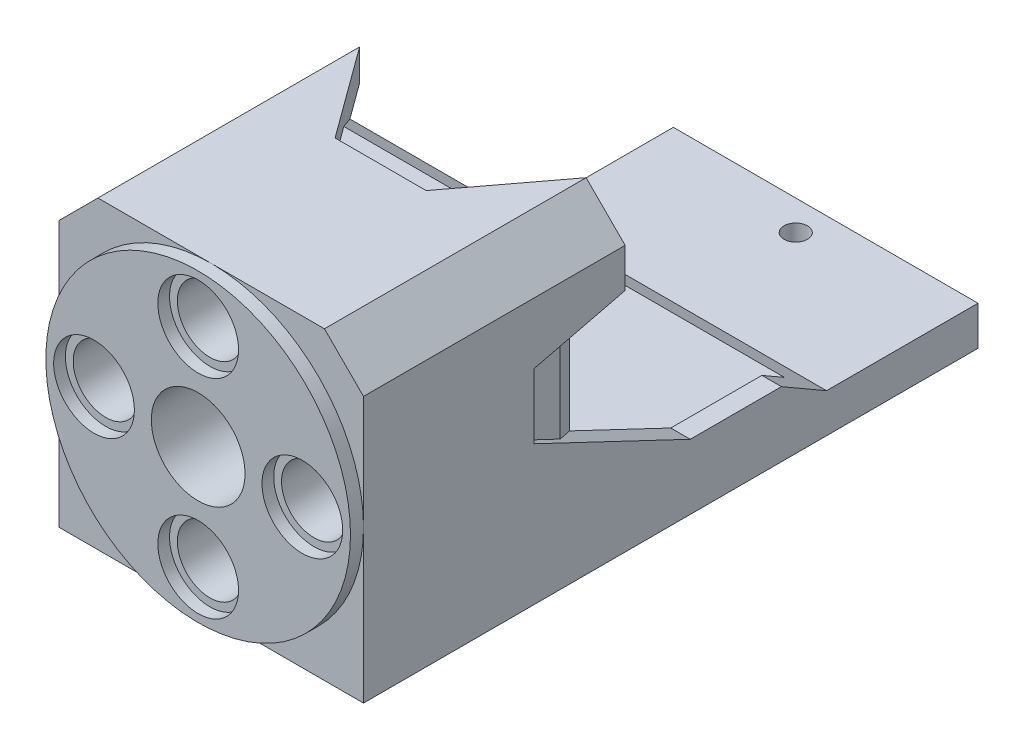
SolidWorks part; units mm, degrees
ref_plane "前视基准面" through (0, 0, 0) normal (0, 0, 1) x (1, 0, 0)
ref_plane "上视基准面" through (0, 0, 0) normal (0, 1, 0) x (1, 0, 0)
ref_plane "右视基准面" through (0, 0, 0) normal (1, 0, 0) x (0, 0, -1)
other "Configuration Table"
sketch "草图1" plane through (0, 0, 0) normal (0, 0, 1) x (1, 0, 0)
  circle A0 centre (0, 0) radius 3.2
  circle A1 centre (-8, 0) radius 2.5
  circle A2 centre (-8, 0) radius 3.1
  circle A3 centre (8, 0) radius 2.5
  circle A4 centre (8, 0) radius 3.1
  circle A5 centre (0, -8) radius 2.5
  circle A6 centre (0, -8) radius 3.1
  circle A7 centre (0, 8) radius 2.5
  circle A8 centre (0, 8) radius 3.1
  circle A9 centre (0, 0) radius 11.7
  dimension "D1" = 6.4
  dimension "D2" = 5
  dimension "D3" = 6.2
  dimension "D8" = 23.4
  dimension "D4" = 8
  dimension "D5" = 8
  dimension "D6" = 8
  dimension "D7" = 8
extrude "凸台-拉伸1" add sketch "草图1" against normal blind 7.7 contours A9
extrude "切除-拉伸1" cut sketch "草图1<3>" against normal through all contours A1 | A7 | A3 | A5 region at (-8, 0, 0) region at (8, 0, 0) region at (0, -8, 0) region at (0, 8, 0)
sketch "草图1<3>" plane through (0, 0, 0) normal (0, 0, 1) x (1, 0, 0) same geometry as "草图1"
extrude "切除-拉伸2" cut sketch "草图1<5>" against normal blind 0.9 contours A2 A1 | A8 A7 | A4 A3 | A6 A5 region at (-11.0123, 0, 0) region at (4.9877, 0, 0) region at (-3.0123, -8, 0) region at (-3.0123, 8, 0)
sketch "草图1<5>" plane through (0, 0, 0) normal (0, 0, 1) x (1, 0, 0) same geometry as "草图1"
extrude "切除-拉伸3" cut sketch "草图1<6>" along normal blind 0.9 from surface contours A2 A1 | A4 A3 | A6 A5 | A8 A7 region at (-11.0123, 0, 0) region at (4.9877, 0, 0) region at (-3.0123, -8, 0) region at (-3.0123, 8, 0) starting at face at (-5.5, 0, -7.7)
sketch "草图1<6>" plane through (0, 0, 0) normal (0, 0, 1) x (1, 0, 0) same geometry as "草图1"
sketch "草图2" plane through (0, 0, 0) normal (0, 0, 1) x (1, 0, 0)
  line L0 (-11.7, 9.3) -> (11.7, 9.3)
  line L1 (11.7, -11.7) -> (-11.7, -11.7)
  line L3 (11.7, 11.7) -> (-11.7, 11.7)
  line L5 (11.7, -11.7) -> (-11.7, 11.7) construction
  line L6 (11.7, 11.7) -> (-11.7, -11.7) construction
  line L7 (-11.7, 11.7) -> (-11.7, 9.3)
  line L8 (11.7, 11.7) -> (11.7, 9.3)
  line L9 (-11.7, -7.7) -> (-11.7, -11.7)
  line L10 (11.7, -7.7) -> (-11.7, -7.7)
  line L12 (11.7, -7.7) -> (11.7, -11.7)
  circle A0 centre (0, 0) radius 11.7 construction
  point P0 (0, 0)
  dimension "D1" = 2.4
  dimension "D2" = 23.4
  dimension "D3" = 4
extrude "凸台-拉伸3" add sketch "草图2" against normal blind 40.5 from surface starting at face at (11.1, 0, -7.7)
sketch "草图3" plane through (0, 0, 0) normal (0, 0, 1) x (1, 0, 0)
  line L0 (-11.7, -11.7) -> (0, -11.7) construction
  line L1 (-11.7, 11.7) -> (-10.2, 11.7)
  line L2 (-11.7, 11.7) -> (-11.7, -11.7)
  line L3 (-11.7, -11.7) -> (-10.2, -11.7)
  line L4 (-10.2, 11.7) -> (-10.2, -11.7)
  line L6 (11.7, -11.7) -> (10.2, -11.7)
  line L7 (11.7, -11.7) -> (11.7, 11.7)
  line L8 (11.7, 11.7) -> (10.2, 11.7)
  line L9 (10.2, -11.7) -> (10.2, 11.7)
  dimension "D1" = 1.5
extrude "凸台-拉伸4" add sketch "草图3" against normal blind 40.3 from surface starting at face at (11.1, 0, -7.7)
sketch "草图4" plane through (0, 0, 0) normal (0, 0, 1) x (1, 0, 0)
  line L1 (-11.7, 11.7) -> (11.7, 11.7)
  line L2 (-11.7, 11.7) -> (-11.7, -11.7)
  line L3 (-11.7, -11.7) -> (11.7, -11.7)
  line L4 (11.7, 11.7) -> (11.7, -11.7)
  circle A0 centre (0, 0) radius 11.7
  circle A1 centre (0, 0) radius 11.7 construction
  circle M5 centre (0, 0) radius 11.7
extrude "凸台-拉伸5" add sketch "草图4" against normal up to surface (7.7 mm away) from offset 1 contours L1 L2 M5 | L4 L1 M5 | L2 L3 M5 | L4 L3 M5 region at (-9.0866, 9.0866, 0) region at (9.0866, 9.0866, 0) region at (-9.0866, -9.0866, 0) region at (9.0866, -9.0866, 0) up to face at (0, -9.4, -7.7) offset against normal yes
sketch "草图7" plane through (-11.7, 0, 0) normal (-1, 0, 0) x (0, 0, 1)
  line L0 (-48.2, 11.7) -> (-48.2, -8.7)
  line L1 (-48.2, -8.7) -> (-36.5641, -8.7)
  line L2 (-36.5641, -8.7) -> (-33.1, -6.7)
  line L3 (-33.1, -6.7) -> (-26.1, -6.7)
  line L4 (-26.1, -6.7) -> (-14.1, -1)
  line L6 (-14.1, -1) -> (-14.1, 4)
  line L9 (-14.1, 4) -> (-21.1, 5.7)
  line L11 (-21.1, 5.7) -> (-21.1, 11.7)
  line L13 (-21.1, 11.7) -> (-48.2, 11.7)
  line L14 (-48.2, 11.7) -> (-1, 11.7) construction
extrude "切除-拉伸5" cut sketch "草图7" against normal through all
chamfer "倒角1" distance 3 angle 45 2 edges at (11.7, 11.7, -11.05) (-11.7, 11.7, -11.05)
sketch "草图8" plane through (0, 11.7, 0) normal (0, 1, 0) x (1, 0, 0)
  line L0 (8.7, 21.1) -> (3.4148, 14.1)
  line L1 (3.4148, 14.1) -> (-3.5852, 14.1)
  line L2 (-3.5852, 14.1) -> (-8.7, 21.1)
  line L3 (-8.7, 21.1) -> (8.7, 21.1)
extrude "切除-拉伸6" cut sketch "草图8" against normal up to next
sketch "草图12" plane through (0, 0, 0) normal (1, 0, 0) x (0, 0, -1)
  line L0 (14.1, 10.3) -> (16.6, 10.3)
  line L1 (14.1, 9.3) -> (14.1, 11.7) construction
  line L2 (16.6, 10.3) -> (18.3321, 9.3)
  line L3 (21.1, 9.3) -> (14.1, 9.3) construction
  line L4 (18.3321, 9.3) -> (14.1, 9.3)
  line L5 (14.1, 9.3) -> (14.1, 10.3)
  dimension "D1" = 1
  dimension "D2" = 2.5
  dimension "D3" = 30
extrude "凸台-拉伸6" add sketch "草图12" along normal up to next and the other way up to next
sketch "草图13" plane through (0, 0, 0) normal (0, 1, 0) x (1, 0, 0)
  line L0 (10.2, 14.1) -> (11.2, 14.1)
  line L1 (11.7, 14.1) -> (10.2, 14.1) construction
  line L2 (11.2, 14.1) -> (11.2, 16.6)
  line L3 (11.2, 16.6) -> (10.2, 18.3321)
  line L4 (10.2, 18.3321) -> (10.2, 14.1)
  line L6 (-10.2, 14.1) -> (-11.2, 14.1)
  line L7 (-10.2, 14.1) -> (-11.7, 14.1) construction
  line L8 (-11.2, 14.1) -> (-11.2, 16.6)
  line L9 (-11.2, 16.6) -> (-10.2, 18.3321)
  line L10 (-10.2, 18.3321) -> (-10.2, 14.1)
  dimension "D1" = 1
  dimension "D2" = 2.5
  dimension "D3" = 30
  dimension "D4" = 1
  dimension "D5" = 2.5
  dimension "D6" = 30
extrude "凸台-拉伸7" add sketch "草图13" along normal up to next and the other way up to next
sketch "草图18" plane through (0, -11.7, 0) normal (0, -1, 0) x (1, 0, 0)
  line L0 (-11.7, -48.2) -> (11.7, -48.2) construction
  line L1 (0, -48.2) -> (0, -45.9) construction
  point P0 (0, -48.2)
  dimension "D1" = 2.3
hole_wizard "孔1" positions "3D草图1" profile "草图17" legacy end condition through all
sketch3d "3D草图1"
  point P9 (0, -11.7, -45.9)
sketch "草图17" plane through (0, -11.7, -45.9) normal (1, 0, 0) x (0, 0, -1)
  line L0 (0, 0) -> (0, 23.4)
  line L1 (0, 23.4) -> (0.9, 23.4)
  line L2 (0.9, 23.4) -> (0.9, 1.35)
  line L3 (0.9, 1.35) -> (1.835, 1.35)
  line L4 (1.835, 1.35) -> (1.835, 0)
  line L5 (1.835, 0) -> (0, 0)
  line L6 (0, 110) -> (0, -10) construction
  dimension "直径" = 1.8
  dimension "深度" = 23.4
  dimension "柱坑直径" = 3.67
  dimension "柱坑深度" = 1.35
sketch "草图19" plane through (0, 0, 0) normal (0, 0, 1) x (1, 0, 0)
  circle A0 centre (0, 0) radius 3.6
  dimension "D1" = 7.2
extrude "切除-拉伸7" cut sketch "草图19" against normal up to next
